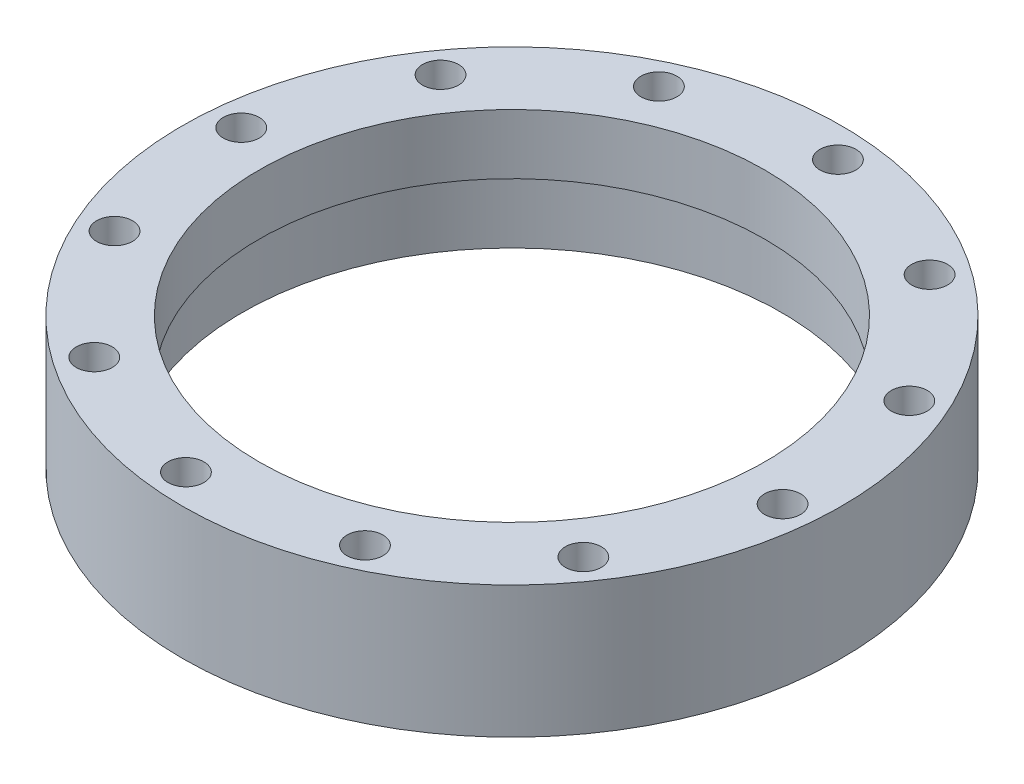
SolidWorks part; units mm, degrees
ref_plane "Front Plane" through (0, 0, 0) normal (0, 0, 1) x (1, 0, 0)
ref_plane "Top Plane" through (0, 0, 0) normal (0, 1, 0) x (1, 0, 0)
ref_plane "Right Plane" through (0, 0, 0) normal (1, 0, 0) x (0, 0, -1)
sketch "Sketch1" plane through (0, 0, 0) normal (0, 1, 0) x (1, 0, 0)
  circle A0 centre (0, 0) radius 27.5
  circle A1 centre (0, 0) radius 25 construction
  circle A2 centre (0, 0) radius 22.5
  circle A3 centre (2.3086, 24.8932) radius 1.5
  circle A4 centre (14.4459, 20.4038) radius 1.5
  circle A5 centre (22.7124, 10.4472) radius 1.5
  circle A6 centre (24.8932, -2.3086) radius 1.5
  circle A7 centre (20.4038, -14.4459) radius 1.5
  circle A8 centre (10.4472, -22.7124) radius 1.5
  circle A9 centre (-2.3086, -24.8932) radius 1.5
  circle A10 centre (-14.4459, -20.4038) radius 1.5
  circle A11 centre (-22.7124, -10.4472) radius 1.5
  circle A12 centre (-24.8932, 2.3086) radius 1.5
  circle A13 centre (-20.4038, 14.4459) radius 1.5
  circle A14 centre (-10.4472, 22.7124) radius 1.5
  point P31 (0, 0)
  dimension "D1" = 55
  dimension "D2" = 50
  dimension "D3" = 45
  dimension "D4" = 3
  dimension "D5" = 12
extrude "Boss-Extrude1" add sketch "Sketch1" along normal blind 11
sketch "Sketch2" plane through (0, 11, 0) normal (0, 1, 0) x (1, 0, 0)
  circle A0 centre (0, 0) radius 22.5
  circle A1 centre (0, 0) radius 21.1
  dimension "D1" = 42.2
extrude "Boss-Extrude2" add sketch "Sketch2" against normal blind 5
